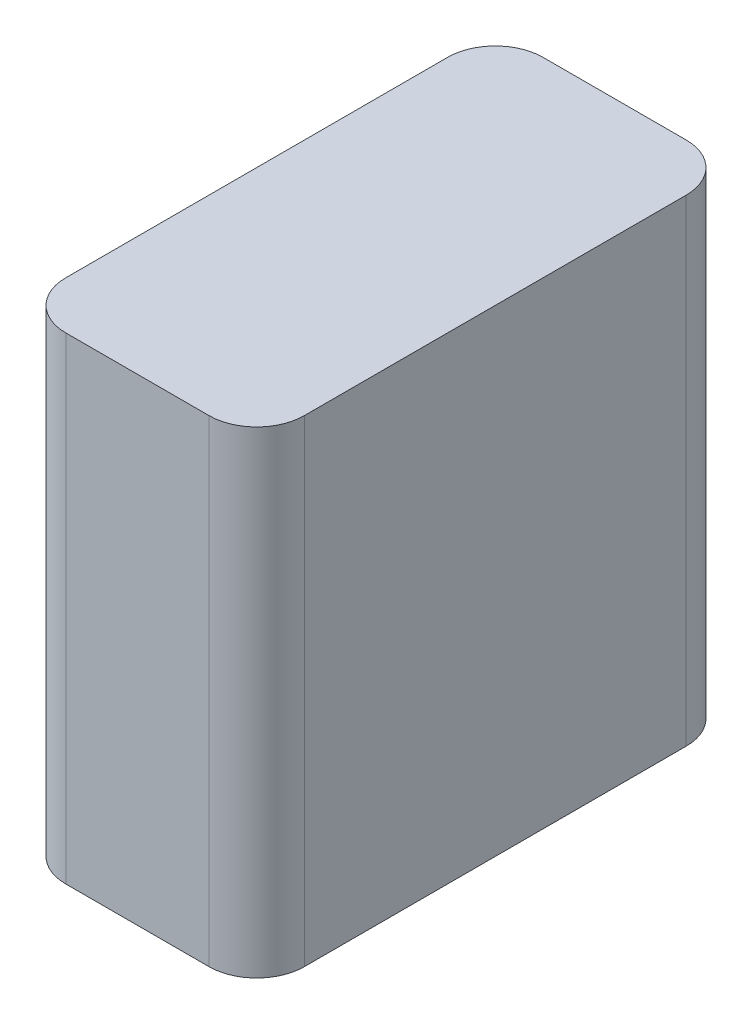
SolidWorks part; units mm, degrees
material "ABS"
ref_plane "前视基准面" through (0, 0, 0) normal (0, 0, 1) x (1, 0, 0)
ref_plane "上视基准面" through (0, 0, 0) normal (0, 1, 0) x (1, 0, 0)
ref_plane "右视基准面" through (0, 0, 0) normal (1, 0, 0) x (0, 0, -1)
ref_plane "ButtonTop" through (0, 0, 0) normal (0, 1, 0) x (1, 0, 0)
ref_plane "CenterV" through (0, 0, 0) normal (1, 0, 0) x (0, 0, -1)
ref_plane "CenterH" through (0, 0, 0) normal (0, 0, 1) x (1, 0, 0)
sketch "Circle" plane through (0, 0, 0) normal (0, 1, 0) x (1, 0, 0)
  line L0 (0, 0) -> (-200, 0) construction
  dimension "R" = 200
ref_axis "CenterAxis" through (-200, 0, 0) along (0, 1, 0)
sketch "SRound" [suppressed] plane through (0, 0, 0) normal (0, 1, 0) x (1, 0, 0)
  circle A0 centre (0, 0) radius 5
  dimension "D1" = 10
extrude "FRound" [suppressed] add sketch "SRound" against normal blind 20
sketch "RoundCut" [suppressed] plane through (0, 0, 0) normal (0, 1, 0) x (1, 0, 0)
  circle A0 centre (0, 0) radius 5.5
  dimension "D1" = 11
sketch "SRectangle" plane through (0, 0, 0) normal (0, 1, 0) x (1, 0, 0)
  line L1 (-5, -10) -> (5, -10)
  line L2 (-5, -10) -> (-5, 10)
  line L3 (-5, 10) -> (5, 10)
  line L4 (5, -10) -> (5, 10)
  line L5 (-5, -10) -> (5, 10) construction
  line L6 (-5, 10) -> (5, -10) construction
  point P0 (0, 0)
  dimension "D1" = 10
  dimension "D2" = 20
extrude "FRectangle" add sketch "SRectangle" against normal blind 20
fillet "FRRectangle" radius 2 4 edges at (-5, -10, -10) (5, -10, -10) (5, -10, 10) (-5, -10, 10)
sketch "RectangleCut" plane through (0, 0, 0) normal (0, 1, 0) x (1, 0, 0)
  line L0 (3.25, 10.25) -> (-3.25, 10.25)
  line L1 (-5.25, 8.25) -> (-5.25, -8.25)
  line L2 (-3.25, -10.25) -> (3.25, -10.25)
  line L3 (5.25, -8.25) -> (5.25, 8.25)
  line L4 (-5, -10) -> (5, -10)
  line L5 (5, -10) -> (5, 10)
  line L6 (5, 10) -> (-5, 10)
  line L7 (-5, 10) -> (-5, -10)
  line L8 (-5, -10) -> (5, -10) construction
  line L9 (5, -10) -> (5, 10) construction
  line L10 (5, 10) -> (-5, 10) construction
  line L11 (-5, 10) -> (-5, -10) construction
  line L12 (-5.25, 10.25) -> (-5.25, -10.25) construction
  line L13 (-5.25, -10.25) -> (5.25, -10.25) construction
  line L14 (5.25, -10.25) -> (5.25, 10.25) construction
  line L15 (5.25, 10.25) -> (-5.25, 10.25) construction
  arc A0 (-5.25, -8.25) -> (-3.25, -10.25) centre (-3.25, -8.25) ccw
  arc A1 (3.25, -10.25) -> (5.25, -8.25) centre (3.25, -8.25) ccw
  arc A2 (5.25, 8.25) -> (3.25, 10.25) centre (3.25, 8.25) ccw
  arc A3 (-5.25, 8.25) -> (-3.25, 10.25) centre (-3.25, 8.25) cw
  dimension "D3" = 2
  dimension "D1" = 0
  dimension "D2" = 0.25
equation "\"BtnH\"= 20"
equation "\"D1@FRound\"=\"BtnH\""
equation "\"D1@RoundCut\"=\"D1@SRound\"+1"
equation "\"D1@FRectangle\"=\"BtnH\""
